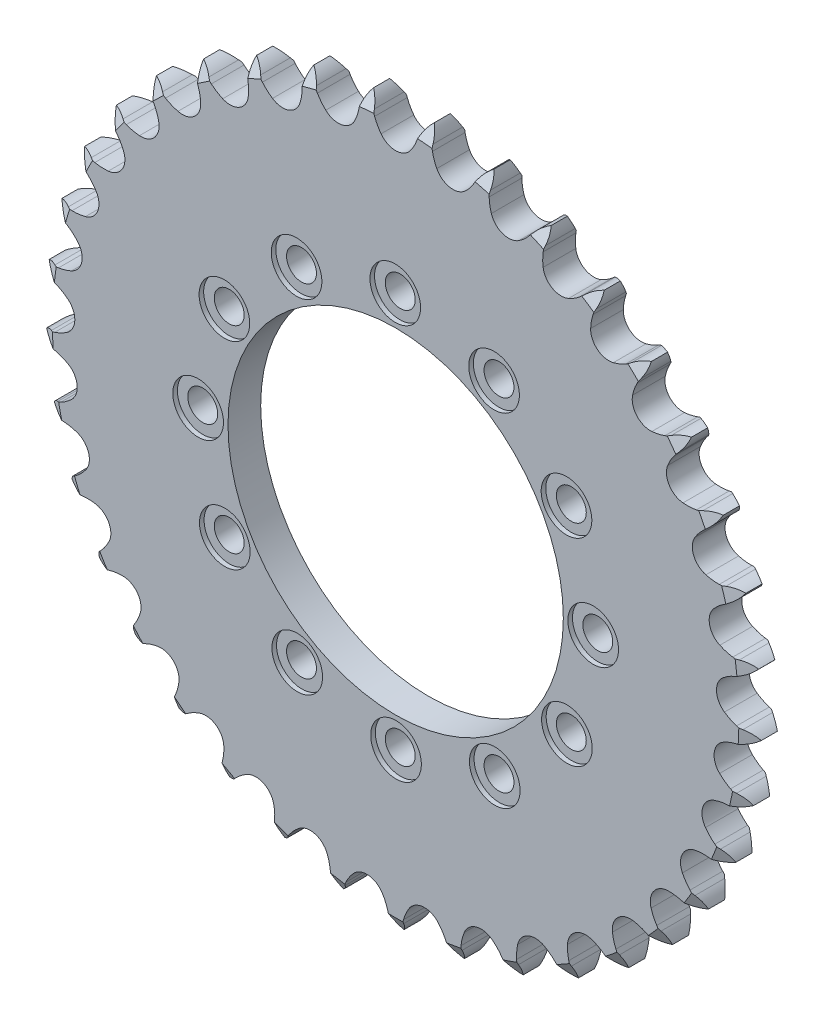
SolidWorks part; units mm, degrees
material "7075-T6 (SN)"
ref_plane "Front Plane" through (0, 0, 0) normal (0, 0, 1) x (1, 0, 0)
ref_plane "Top Plane" through (0, 0, 0) normal (0, 1, 0) x (1, 0, 0)
ref_plane "Right Plane" through (0, 0, 0) normal (1, 0, 0) x (0, 0, -1)
sketch "Work Sketch" plane through (0, 0, 0) normal (0, 0, 1) x (1, 0, 0)
  line L0 (0, 0) -> (0, 160.4542) construction
  line L1 (-112.0919, 74.8768) -> (87.2579, 74.8768) construction
  line L2 (5.0965, 120.8822) -> (5.0965, 112.9699) construction
  line L3 (-12.8497, 78.6648) -> (16.7256, 78.6648) construction
  line L4 (5.0965, 78.6648) -> (-6.0814, 70.3569) construction
  line L5 (5.0965, 78.6648) -> (-4.646, 75.0928) construction
  line L6 (-4.646, 75.0928) -> (-6.919, 81.2921)
  line L7 (-11.5114, 73.9344) -> (-7.1525, 73.9344) construction
  line L8 (-11.0725, 124.7602) -> (-11.0725, 110.2345) construction
  line L9 (0, 0) -> (-3.6257, 42.5992) construction
  circle A0 centre (0, 0) radius 74.8768
  circle A1 centre (0, 74.8768) radius 4.0088
  arc A2 (-4.646, 75.0928) -> (-3.2175, 72.4855) centre (5.0746, 78.7238) ccw
  circle A3 centre (-11.0725, 73.9344) radius 6.4324
  point P23 (-3.2175, 72.4855)
  dimension "D1" = 149.7537
  dimension "D8" = 10.3767
  dimension "D2" = 8.0177
  dimension "D3" = 5.0965
  dimension "D4" = 3.788
  dimension "D5" = 36.622
  dimension "D6" = 16.486
  dimension "D7" = 10.3767
  dimension "D9" = 0.9424
  dimension "D10" = 11.0725
  dimension "D11" = 4.865
sketch "Teeth Sketch" plane through (0, 0, 0) normal (0, 0, 1) x (1, 0, 0)
  line L0 (5.0332, 76.1487) -> (4.646, 75.0928)
  line L1 (-7.8902, 92.7037) -> (-5.0419, 59.2379) construction
  line L2 (0, 0) -> (-11.4893, 132.2573) construction
  line L3 (7.9084, 75.904) -> (8.1115, 74.7978)
  line L4 (16961.1849, -199279.4977) -> (-16964.8106, 199322.0969) construction
  line L5 (0, 146.3285) -> (0, 56.9858) construction
  line L6 (17.83, 74.2028) -> (17.27, 73.2274)
  line L7 (0, -200000) -> (0, 200160.4542) construction
  line L8 (20.6225, 73.4756) -> (20.6357, 72.3511)
  line L9 (-4.646, 75.0928) -> (-6.919, 81.2921) construction
  line L10 (43.9221, 62.4084) -> (43.56, 61.3436)
  line L11 (-5.0332, 76.1487) -> (-4.646, 75.0928)
  line L12 (30.1138, 70.1221) -> (29.397, 69.2555)
  line L13 (32.7433, 68.9336) -> (32.5663, 67.8229)
  line L14 (41.5314, 64.0242) -> (40.6784, 63.2912)
  line L15 (51.7541, 56.0845) -> (50.7896, 55.5061)
  line L16 (53.8374, 54.0878) -> (53.3005, 53.0996)
  line L17 (60.488, 46.5312) -> (59.4396, 46.1242)
  line L18 (62.2039, 44.2112) -> (61.5077, 43.3279)
  line L19 (67.4818, 35.6394) -> (66.3796, 35.4154)
  line L20 (68.7809, 33.0628) -> (67.9454, 32.3098)
  line L21 (72.5342, 23.7223) -> (71.4101, 23.6878)
  line L22 (73.3792, 20.9632) -> (72.4285, 20.3623)
  line L23 (75.4999, 11.1227) -> (74.3862, 11.2787)
  line L24 (75.8665, 8.2605) -> (74.8279, 7.8289)
  line L25 (76.2937, -1.7968) -> (75.2223, -1.4548)
  line L26 (76.1712, -4.6798) -> (75.0747, -4.9297)
  line L27 (74.8926, -14.6647) -> (73.8944, -14.1465)
  line L28 (74.2847, -17.4855) -> (73.1617, -17.5465)
  line L29 (71.337, -27.1106) -> (70.4407, -26.4313)
  line L30 (70.2611, -29.7882) -> (69.1439, -29.6585)
  line L31 (65.7292, -38.7767) -> (64.9606, -37.9556)
  line L32 (64.2162, -41.2339) -> (63.1371, -40.9172)
  line L33 (58.2304, -49.3272) -> (57.6117, -48.3881)
  line L34 (56.324, -51.4934) -> (55.3138, -50.9989)
  line L35 (49.0565, -58.4587) -> (48.6054, -57.4285)
  line L36 (46.8114, -60.2715) -> (45.8993, -59.6134)
  line L37 (38.4713, -65.9084) -> (38.2008, -64.8168)
  line L38 (35.9521, -67.3157) -> (35.1644, -66.513)
  line L39 (26.7794, -71.462) -> (26.6972, -70.3404)
  line L40 (24.0586, -72.4234) -> (23.4179, -71.499)
  line L41 (14.317, -74.9599) -> (14.4256, -73.8404)
  line L42 (11.4729, -75.4475) -> (10.9976, -74.4282)
  line L43 (1.4428, -76.3012) -> (1.739, -75.2163)
  line L44 (-1.4428, -76.3012) -> (-1.739, -75.2163)
  line L45 (-11.4729, -75.4475) -> (-10.9976, -74.4282)
  line L46 (-14.317, -74.9599) -> (-14.4256, -73.8404)
  line L47 (-24.0586, -72.4234) -> (-23.4179, -71.499)
  line L48 (-26.7794, -71.462) -> (-26.6972, -70.3404)
  line L49 (-35.9521, -67.3157) -> (-35.1644, -66.513)
  line L50 (-38.4713, -65.9084) -> (-38.2008, -64.8168)
  line L51 (-46.8114, -60.2715) -> (-45.8993, -59.6134)
  line L52 (-49.0565, -58.4587) -> (-48.6054, -57.4285)
  line L53 (-56.324, -51.4934) -> (-55.3138, -50.9989)
  line L54 (-58.2304, -49.3272) -> (-57.6117, -48.3881)
  line L55 (-64.2162, -41.2339) -> (-63.1371, -40.9172)
  line L56 (-65.7292, -38.7767) -> (-64.9606, -37.9556)
  line L57 (-70.2611, -29.7882) -> (-69.1439, -29.6585)
  line L58 (-71.337, -27.1106) -> (-70.4407, -26.4313)
  line L59 (-74.2847, -17.4855) -> (-73.1617, -17.5465)
  line L60 (-74.8926, -14.6647) -> (-73.8944, -14.1465)
  line L61 (-76.1712, -4.6798) -> (-75.0747, -4.9297)
  line L62 (-76.2937, -1.7968) -> (-75.2223, -1.4548)
  line L63 (-75.8665, 8.2605) -> (-74.8279, 7.8289)
  line L64 (-75.4999, 11.1227) -> (-74.3862, 11.2787)
  line L65 (-73.3792, 20.9632) -> (-72.4285, 20.3623)
  line L66 (-72.5342, 23.7223) -> (-71.4101, 23.6878)
  line L67 (-68.7809, 33.0628) -> (-67.9454, 32.3098)
  line L68 (-67.4818, 35.6394) -> (-66.3796, 35.4154)
  line L69 (-62.2039, 44.2112) -> (-61.5077, 43.3279)
  line L70 (-60.488, 46.5312) -> (-59.4396, 46.1242)
  line L71 (-53.8374, 54.0878) -> (-53.3005, 53.0996)
  line L72 (-51.7541, 56.0845) -> (-50.7896, 55.5061)
  line L73 (-43.9221, 62.4084) -> (-43.56, 61.3436)
  line L74 (-41.5314, 64.0242) -> (-40.6784, 63.2912)
  line L75 (-32.7433, 68.9336) -> (-32.5663, 67.8229)
  line L76 (-30.1138, 70.1221) -> (-29.397, 69.2555)
  line L77 (-20.6225, 73.4756) -> (-20.6357, 72.3511)
  line L78 (-17.83, 74.2028) -> (-17.27, 73.2274)
  line L79 (-7.9084, 75.904) -> (-8.1115, 74.7978)
  arc A0 (-6.8438, 78.7815) -> (-5.0332, 76.1487) centre (-11.0725, 73.9344) cw
  circle A1 centre (-11.0725, 73.9344) radius 6.4324 construction
  arc A2 (-3.2175, 72.4855) -> (-4.646, 75.0928) centre (5.0746, 78.7238) cw
  arc A3 (-4.646, 75.0928) -> (-3.2175, 72.4855) centre (5.0746, 78.7238) ccw construction
  circle A4 centre (0, 74.8768) radius 4.0088 construction
  arc A5 (-3.2175, 72.4855) -> (3.2175, 72.4855) centre (0, 74.8768) ccw
  arc A6 (3.2175, 72.4855) -> (4.646, 75.0928) centre (-5.0746, 78.7238) ccw
  arc A7 (6.8438, 78.7815) -> (5.0332, 76.1487) centre (11.0725, 73.9344) ccw
  arc A8 (6.5688, 78.8049) -> (7.9084, 75.904) centre (1.5818, 74.7422) cw
  arc A9 (9.0789, 71.9866) -> (8.1115, 74.7978) centre (18.306, 76.7339) cw
  arc A10 (9.0789, 71.9866) -> (15.4213, 70.8991) centre (12.6542, 73.7998) ccw
  arc A11 (15.4213, 70.8991) -> (17.27, 73.2274) centre (8.3028, 78.4491) ccw
  arc A12 (20.0595, 76.4917) -> (17.83, 74.2028) centre (23.4082, 70.9997) ccw
  arc A13 (19.7924, 76.5613) -> (20.6225, 73.4756) centre (14.1905, 73.3998) cw
  arc A14 (21.1141, 69.4168) -> (20.6357, 72.3511) centre (31.0108, 72.5364) cw
  arc A15 (21.1141, 69.4168) -> (27.1815, 67.273) centre (24.9445, 70.5997) ccw
  arc A16 (27.1815, 67.273) -> (29.397, 69.2555) centre (21.4413, 75.9175) ccw
  arc A17 (32.6981, 72.0014) -> (30.1138, 70.1221) centre (35.0705, 66.0224) ccw
  arc A18 (32.4466, 72.1151) -> (32.7433, 68.9336) centre (26.391, 69.9458) cw
  arc A19 (32.5419, 64.85) -> (32.5663, 67.8229) centre (42.8234, 66.2522) cw
  arc A20 (32.5419, 64.85) -> (38.1597, 61.7117) centre (36.5171, 65.3685) ccw
  arc A21 (38.1597, 61.7117) -> (40.6784, 63.2912) centre (33.963, 71.2019) ccw
  arc A22 (44.3961, 65.4397) -> (41.5314, 64.0242) centre (45.7239, 59.1458) ccw
  arc A23 (44.1674, 65.5943) -> (43.9221, 62.4084) centre (37.8323, 64.4796) cw
  arc A24 (43.0335, 58.4176) -> (43.56, 61.3436) centre (53.4041, 58.062) cw
  arc A25 (43.0335, 58.4176) -> (48.0401, 54.375) centre (47.0391, 58.2569) ccw
  arc A26 (48.0401, 54.375) -> (50.7896, 55.5061) centre (45.5077, 64.4379) ccw
  arc A27 (54.8169, 56.9954) -> (51.7541, 56.0845) centre (55.0619, 50.5677) ccw
  arc A28 (54.6176, 57.1864) -> (53.8374, 54.0878) centre (48.1852, 57.1584) cw
  arc A29 (52.2871, 50.3046) -> (53.3005, 53.0996) centre (62.4485, 48.2015) cw
  arc A30 (52.2871, 50.3046) -> (56.5385, 45.4741) centre (56.208, 49.4692) ccw
  arc A31 (56.5385, 45.4741) -> (59.4396, 46.1242) centre (55.7431, 55.8202) ccw
  arc A32 (63.6606, 46.9115) -> (60.488, 46.5312) centre (62.8158, 40.5348) ccw
  arc A33 (63.4965, 47.1334) -> (62.2039, 44.2112) centre (57.152, 48.1929) cw
  arc A34 (60.0365, 40.7444) -> (61.5077, 43.3279) centre (69.6963, 36.9543) cw
  arc A35 (60.0365, 40.7444) -> (63.4104, 35.2649) centre (63.7598, 39.2585) ccw
  arc A36 (63.4104, 35.2649) -> (66.3796, 35.4154) centre (64.375, 45.5967) ccw
  arc A37 (70.673, 35.478) -> (67.4818, 35.6394) centre (68.7627, 29.3358) ccw
  arc A38 (70.5488, 35.7245) -> (68.7809, 33.0628) centre (64.4745, 37.841) cw
  arc A39 (66.0588, 30.0121) -> (67.9454, 32.3098) centre (74.9391, 24.644) cw
  arc A40 (66.0588, 30.0121) -> (68.4581, 24.0412) centre (69.4774, 27.9183) ccw
  arc A41 (68.4581, 24.0412) -> (71.4101, 23.6878) centre (71.1549, 34.0614) ccw
  arc A42 (75.6523, 23.0239) -> (72.5342, 23.7223) centre (72.7314, 17.2929) ccw
  arc A43 (75.5714, 23.2878) -> (73.3792, 20.9632) centre (69.9423, 26.4004) cw
  arc A44 (70.1807, 18.4164) -> (72.4285, 20.3623) centre (78.026, 11.6248) cw
  arc A45 (70.1807, 18.4164) -> (71.5364, 12.1259) centre (73.1963, 15.775) ccw
  arc A46 (71.5364, 12.1259) -> (74.3862, 11.2787) centre (75.8878, 21.5462) ccw
  arc A47 (78.4551, 9.9074) -> (75.4999, 11.1227) centre (74.6077, 4.7525) ccw
  arc A48 (78.4201, 10.1812) -> (75.8665, 8.2605) centre (73.3979, 14.2004) cw
  arc A49 (72.2836, 6.2909) -> (74.8279, 7.8289) centre (78.8683, -1.7289) cw
  arc A50 (72.2836, 6.2909) -> (72.5567, -0.1382) centre (74.8094, 3.1779) ccw
  arc A51 (72.5567, -0.1382) -> (75.2223, -1.4548) centre (78.4375, 8.4112) ccw
  arc A52 (79.001, -3.4941) -> (76.2937, -1.7968) centre (74.3377, -7.9246) ccw
  arc A53 (79.0127, -3.2183) -> (76.1712, -4.6798) centre (74.742, 1.5918) cw
  arc A54 (72.307, -6.0155) -> (75.0747, -4.9297) centre (77.4416, -15.0328) cw
  arc A55 (72.307, -6.0155) -> (71.4897, -12.3983) centre (74.2704, -9.5107) ccw
  arc A56 (71.4897, -12.3983) -> (73.8944, -14.1465) centre (78.7308, -4.9658) ccw
  arc A57 (77.2741, -16.795) -> (74.8926, -14.6647) centre (71.9292, -20.3738) ccw
  arc A58 (77.3323, -16.5252) -> (74.2847, -17.4855) centre (73.9359, -11.0626) cw
  arc A59 (70.2503, -18.149) -> (73.1617, -17.5465) centre (73.7872, -27.9043) cw
  arc A60 (70.2503, -18.149) -> (68.366, -24.3018) centre (71.5947, -21.9256) ccw
  arc A61 (68.366, -24.3018) -> (70.4407, -26.4313) centre (76.7591, -18.2) ccw
  arc A62 (73.3243, -29.6129) -> (71.337, -27.1106) centre (67.4514, -32.2368) ccw
  arc A63 (73.4272, -29.3567) -> (70.2611, -29.7882) centre (71.0028, -23.3987) cw
  arc A64 (66.1727, -29.7603) -> (69.1439, -29.6585) centre (68.0099, -39.973) cw
  arc A65 (66.1727, -29.7603) -> (63.2756, -35.5062) centre (66.8595, -33.7098) ccw
  arc A66 (63.2756, -35.5062) -> (64.9606, -37.9556) centre (72.5792, -30.9105) ccw
  arc A67 (67.265, -41.5788) -> (65.7292, -38.7767) centre (61.0331, -43.1725) ccw
  arc A68 (67.4097, -41.3437) -> (64.2162, -41.2339) centre (66.0271, -35.0616) cw
  arc A69 (60.1913, -40.5154) -> (63.1371, -40.9172) centre (60.2762, -50.8918) cw
  arc A70 (60.1913, -40.5154) -> (56.3649, -45.6891) centre (60.2008, -44.5243) ccw
  arc A71 (56.3649, -45.6891) -> (57.6117, -48.3881) centre (66.3113, -42.7318) ccw
  arc A72 (59.2706, -52.3485) -> (58.2304, -49.3272) centre (52.859, -52.8661) ccw
  arc A73 (59.4529, -52.1413) -> (56.324, -51.4934) centre (59.1519, -45.7159) cw
  arc A74 (52.4784, -50.105) -> (55.3138, -50.9989) centre (50.8084, -60.3465) cw
  arc A75 (52.4784, -50.105) -> (47.8326, -54.5576) centre (51.8102, -54.0578) ccw
  arc A76 (47.8326, -54.5576) -> (48.6054, -57.4285) centre (58.1357, -53.3238) ccw
  arc A77 (49.5711, -61.6123) -> (49.0565, -58.4587) centre (43.1643, -61.0389) ccw
  arc A78 (49.7858, -61.4389) -> (46.8114, -60.2715) centre (50.5751, -55.0551) cw
  arc A79 (43.2557, -58.2532) -> (45.8993, -59.6134) centre (39.879, -68.0651) cw
  arc A80 (43.2557, -58.2532) -> (37.9243, -61.8566) centre (41.9291, -62.0362) ccw
  arc A81 (37.9243, -61.8566) -> (38.2008, -64.8168) centre (48.2877, -62.3818) ccw
  arc A82 (38.4455, -69.1036) -> (38.4713, -65.9084) centre (32.2278, -67.4557) ccw
  arc A83 (38.6865, -68.969) -> (35.9521, -67.3157) centre (40.5432, -62.8104) cw
  arc A84 (32.7887, -64.7255) -> (35.1644, -66.513) centre (27.8023, -73.8256) cw
  arc A85 (32.7887, -64.7255) -> (26.925, -67.3761) centre (30.8419, -68.2299) ccw
  arc A86 (26.925, -67.3761) -> (26.6972, -70.3404) centre (37.0506, -69.6452) ccw
  arc A87 (26.2139, -74.6069) -> (26.7794, -71.462) centre (20.3641, -71.9319) ccw
  arc A88 (26.4742, -74.515) -> (24.0586, -72.4234) centre (29.345, -68.7588) cw
  arc A89 (21.3784, -69.3358) -> (23.4179, -71.499) centre (14.9258, -77.4623) cw
  arc A90 (21.3784, -69.3358) -> (15.1511, -70.9573) centre (18.8673, -72.4608) ccw
  arc A91 (15.1511, -70.9573) -> (14.4256, -73.8404) centre (24.7475, -74.905) ccw
  arc A92 (13.2282, -77.964) -> (14.317, -74.9599) centre (7.9147, -74.3388) ccw
  arc A93 (13.5003, -77.9173) -> (11.4729, -75.4475) centre (17.3027, -72.7291) cw
  arc A94 (9.3531, -71.9515) -> (10.9976, -74.4282) centre (1.6199, -78.8706) cw
  arc A95 (9.3531, -71.9515) -> (2.9413, -72.4972) centre (6.35, -74.6071) ccw
  arc A96 (2.9413, -72.4972) -> (1.739, -75.2163) centre (11.7326, -78.0099) ccw
  arc A97 (-0.138, -79.0781) -> (1.4428, -76.3012) centre (-4.7625, -74.6071) ccw
  arc A98 (0.138, -79.0781) -> (-1.4428, -76.3012) centre (4.7625, -74.6071) cw
  arc A99 (-2.9413, -72.4972) -> (-1.739, -75.2163) centre (-11.7326, -78.0099) cw
  arc A100 (-2.9413, -72.4972) -> (-9.3531, -71.9515) centre (-6.35, -74.6071) ccw
  arc A101 (-9.3531, -71.9515) -> (-10.9976, -74.4282) centre (-1.6199, -78.8706) ccw
  arc A102 (-13.5003, -77.9173) -> (-11.4729, -75.4475) centre (-17.3027, -72.7291) ccw
  arc A103 (-13.2282, -77.964) -> (-14.317, -74.9599) centre (-7.9147, -74.3388) cw
  arc A104 (-15.1511, -70.9573) -> (-14.4256, -73.8404) centre (-24.7475, -74.905) cw
  arc A105 (-15.1511, -70.9573) -> (-21.3784, -69.3358) centre (-18.8673, -72.4608) ccw
  arc A106 (-21.3784, -69.3358) -> (-23.4179, -71.499) centre (-14.9258, -77.4623) ccw
  arc A107 (-26.4742, -74.515) -> (-24.0586, -72.4234) centre (-29.345, -68.7588) ccw
  arc A108 (-26.2139, -74.6069) -> (-26.7794, -71.462) centre (-20.3641, -71.9319) cw
  arc A109 (-26.925, -67.3761) -> (-26.6972, -70.3404) centre (-37.0506, -69.6452) cw
  arc A110 (-26.925, -67.3761) -> (-32.7887, -64.7255) centre (-30.8419, -68.2299) ccw
  arc A111 (-32.7887, -64.7255) -> (-35.1644, -66.513) centre (-27.8023, -73.8256) ccw
  arc A112 (-38.6865, -68.969) -> (-35.9521, -67.3157) centre (-40.5432, -62.8104) ccw
  arc A113 (-38.4455, -69.1036) -> (-38.4713, -65.9084) centre (-32.2278, -67.4557) cw
  arc A114 (-37.9243, -61.8566) -> (-38.2008, -64.8168) centre (-48.2877, -62.3818) cw
  arc A115 (-37.9243, -61.8566) -> (-43.2557, -58.2532) centre (-41.9291, -62.0362) ccw
  arc A116 (-43.2557, -58.2532) -> (-45.8993, -59.6134) centre (-39.879, -68.0651) ccw
  arc A117 (-49.7858, -61.4389) -> (-46.8114, -60.2715) centre (-50.5751, -55.0551) ccw
  arc A118 (-49.5711, -61.6123) -> (-49.0565, -58.4587) centre (-43.1643, -61.0389) cw
  arc A119 (-47.8326, -54.5576) -> (-48.6054, -57.4285) centre (-58.1357, -53.3238) cw
  arc A120 (-47.8326, -54.5576) -> (-52.4784, -50.105) centre (-51.8102, -54.0578) ccw
  arc A121 (-52.4784, -50.105) -> (-55.3138, -50.9989) centre (-50.8084, -60.3465) ccw
  arc A122 (-59.4529, -52.1413) -> (-56.324, -51.4934) centre (-59.1519, -45.7159) ccw
  arc A123 (-59.2706, -52.3485) -> (-58.2304, -49.3272) centre (-52.859, -52.8661) cw
  arc A124 (-56.3649, -45.6891) -> (-57.6117, -48.3881) centre (-66.3113, -42.7318) cw
  arc A125 (-56.3649, -45.6891) -> (-60.1913, -40.5154) centre (-60.2008, -44.5243) ccw
  arc A126 (-60.1913, -40.5154) -> (-63.1371, -40.9172) centre (-60.2762, -50.8918) ccw
  arc A127 (-67.4097, -41.3437) -> (-64.2162, -41.2339) centre (-66.0271, -35.0616) ccw
  arc A128 (-67.265, -41.5788) -> (-65.7292, -38.7767) centre (-61.0331, -43.1725) cw
  arc A129 (-63.2756, -35.5062) -> (-64.9606, -37.9556) centre (-72.5792, -30.9105) cw
  arc A130 (-63.2756, -35.5062) -> (-66.1727, -29.7603) centre (-66.8595, -33.7098) ccw
  arc A131 (-66.1727, -29.7603) -> (-69.1439, -29.6585) centre (-68.0099, -39.973) ccw
  arc A132 (-73.4272, -29.3567) -> (-70.2611, -29.7882) centre (-71.0028, -23.3987) ccw
  arc A133 (-73.3243, -29.6129) -> (-71.337, -27.1106) centre (-67.4514, -32.2368) cw
  arc A134 (-68.366, -24.3018) -> (-70.4407, -26.4313) centre (-76.7591, -18.2) cw
  arc A135 (-68.366, -24.3018) -> (-70.2503, -18.149) centre (-71.5947, -21.9256) ccw
  arc A136 (-70.2503, -18.149) -> (-73.1617, -17.5465) centre (-73.7872, -27.9043) ccw
  arc A137 (-77.3323, -16.5252) -> (-74.2847, -17.4855) centre (-73.9359, -11.0626) ccw
  arc A138 (-77.2741, -16.795) -> (-74.8926, -14.6647) centre (-71.9292, -20.3738) cw
  arc A139 (-71.4897, -12.3983) -> (-73.8944, -14.1465) centre (-78.7308, -4.9658) cw
  arc A140 (-71.4897, -12.3983) -> (-72.307, -6.0155) centre (-74.2704, -9.5107) ccw
  arc A141 (-72.307, -6.0155) -> (-75.0747, -4.9297) centre (-77.4416, -15.0328) ccw
  arc A142 (-79.0127, -3.2183) -> (-76.1712, -4.6798) centre (-74.742, 1.5918) ccw
  arc A143 (-79.001, -3.4941) -> (-76.2937, -1.7968) centre (-74.3377, -7.9246) cw
  arc A144 (-72.5567, -0.1382) -> (-75.2223, -1.4548) centre (-78.4375, 8.4112) cw
  arc A145 (-72.5567, -0.1382) -> (-72.2836, 6.2909) centre (-74.8094, 3.1779) ccw
  arc A146 (-72.2836, 6.2909) -> (-74.8279, 7.8289) centre (-78.8683, -1.7289) ccw
  arc A147 (-78.4201, 10.1812) -> (-75.8665, 8.2605) centre (-73.3979, 14.2004) ccw
  arc A148 (-78.4551, 9.9074) -> (-75.4999, 11.1227) centre (-74.6077, 4.7525) cw
  arc A149 (-71.5364, 12.1259) -> (-74.3862, 11.2787) centre (-75.8878, 21.5462) cw
  arc A150 (-71.5364, 12.1259) -> (-70.1807, 18.4164) centre (-73.1963, 15.775) ccw
  arc A151 (-70.1807, 18.4164) -> (-72.4285, 20.3623) centre (-78.026, 11.6248) ccw
  arc A152 (-75.5714, 23.2878) -> (-73.3792, 20.9632) centre (-69.9423, 26.4004) ccw
  arc A153 (-75.6523, 23.0239) -> (-72.5342, 23.7223) centre (-72.7314, 17.2929) cw
  arc A154 (-68.4581, 24.0412) -> (-71.4101, 23.6878) centre (-71.1549, 34.0614) cw
  arc A155 (-68.4581, 24.0412) -> (-66.0588, 30.0121) centre (-69.4774, 27.9183) ccw
  arc A156 (-66.0588, 30.0121) -> (-67.9454, 32.3098) centre (-74.9391, 24.644) ccw
  arc A157 (-70.5488, 35.7245) -> (-68.7809, 33.0628) centre (-64.4745, 37.841) ccw
  arc A158 (-70.673, 35.478) -> (-67.4818, 35.6394) centre (-68.7627, 29.3358) cw
  arc A159 (-63.4104, 35.2649) -> (-66.3796, 35.4154) centre (-64.375, 45.5967) cw
  arc A160 (-63.4104, 35.2649) -> (-60.0365, 40.7444) centre (-63.7598, 39.2585) ccw
  arc A161 (-60.0365, 40.7444) -> (-61.5077, 43.3279) centre (-69.6963, 36.9543) ccw
  arc A162 (-63.4965, 47.1334) -> (-62.2039, 44.2112) centre (-57.152, 48.1929) ccw
  arc A163 (-63.6606, 46.9115) -> (-60.488, 46.5312) centre (-62.8158, 40.5348) cw
  arc A164 (-56.5385, 45.4741) -> (-59.4396, 46.1242) centre (-55.7431, 55.8202) cw
  arc A165 (-56.5385, 45.4741) -> (-52.2871, 50.3046) centre (-56.208, 49.4692) ccw
  arc A166 (-52.2871, 50.3046) -> (-53.3005, 53.0996) centre (-62.4485, 48.2015) ccw
  arc A167 (-54.6176, 57.1864) -> (-53.8374, 54.0878) centre (-48.1852, 57.1584) ccw
  arc A168 (-54.8169, 56.9954) -> (-51.7541, 56.0845) centre (-55.0619, 50.5677) cw
  arc A169 (-48.0401, 54.375) -> (-50.7896, 55.5061) centre (-45.5077, 64.4379) cw
  arc A170 (-48.0401, 54.375) -> (-43.0335, 58.4176) centre (-47.0391, 58.2569) ccw
  arc A171 (-43.0335, 58.4176) -> (-43.56, 61.3436) centre (-53.4041, 58.062) ccw
  arc A172 (-44.1674, 65.5943) -> (-43.9221, 62.4084) centre (-37.8323, 64.4796) ccw
  arc A173 (-44.3961, 65.4397) -> (-41.5314, 64.0242) centre (-45.7239, 59.1458) cw
  arc A174 (-38.1597, 61.7117) -> (-40.6784, 63.2912) centre (-33.963, 71.2019) cw
  arc A175 (-38.1597, 61.7117) -> (-32.5419, 64.85) centre (-36.5171, 65.3685) ccw
  arc A176 (-32.5419, 64.85) -> (-32.5663, 67.8229) centre (-42.8234, 66.2522) ccw
  arc A177 (-32.4466, 72.1151) -> (-32.7433, 68.9336) centre (-26.391, 69.9458) ccw
  arc A178 (-32.6981, 72.0014) -> (-30.1138, 70.1221) centre (-35.0705, 66.0224) cw
  arc A179 (-27.1815, 67.273) -> (-29.397, 69.2555) centre (-21.4413, 75.9175) cw
  arc A180 (-27.1815, 67.273) -> (-21.1141, 69.4168) centre (-24.9445, 70.5997) ccw
  arc A181 (-21.1141, 69.4168) -> (-20.6357, 72.3511) centre (-31.0108, 72.5364) ccw
  arc A182 (-19.7924, 76.5613) -> (-20.6225, 73.4756) centre (-14.1905, 73.3998) ccw
  arc A183 (-20.0595, 76.4917) -> (-17.83, 74.2028) centre (-23.4082, 70.9997) cw
  arc A184 (-15.4213, 70.8991) -> (-17.27, 73.2274) centre (-8.3028, 78.4491) cw
  arc A185 (-15.4213, 70.8991) -> (-9.0789, 71.9866) centre (-12.6542, 73.7998) ccw
  arc A186 (-9.0789, 71.9866) -> (-8.1115, 74.7978) centre (-18.306, 76.7339) ccw
  arc A187 (-6.5688, 78.8049) -> (-7.9084, 75.904) centre (-1.5818, 74.7422) ccw
  point P77 (0, 0)
  dimension "D1" = 4.865
  dimension "D2" = 4.965
  dimension "D3" = 37
extrude "Extrusion" add sketch "Teeth Sketch" along normal blind 7.2136
hole_wizard "M6 Clearance Hole1" positions "Sketch6" profile "Sketch7" hole size "M6" standard "ANSI Metric"
sketch "Sketch6" plane through (0, 0, 0) normal (0, 0, -1) x (-1, 0, 0)
  circle A0 centre (0, 0) radius 43.5
  point P0 (0, 43.5)
  dimension "D1" = 87
sketch "Sketch7" plane through (0, 43.5, 0) normal (1, 0, 0) x (0, 1, 0)
  line L0 (0, 0) -> (0, 19.2548)
  line L1 (0, 19.2548) -> (3.3, 17.272)
  line L2 (3.3, 17.272) -> (3.3, 0)
  line L5 (3.3, 0) -> (0, 0)
  line L10 (0, 19.2548) -> (-3.3, 17.272) construction
  line L11 (0, -6.35) -> (0, 107.95) construction
  dimension "Hole Dia." = 6.6
  dimension "Hole Depth" = 17.272
  dimension "Drill Angle" = 118
pattern_circular "CirPattern1" count 12 over 360 about axis through (0, -0.0877, 0) along (0, 0, 1) of "M6 Clearance Hole1"
sketch "Sketch8" plane through (0, 0, 0) normal (0, 0, -1) x (-1, 0, 0)
  circle A0 centre (0, 0) radius 37
  dimension "D1" = 74
extrude "Cut-Extrude1" cut sketch "Sketch8" against normal through all both and the other way through all
ref_plane "Sprocket Center Plane" through (0, 0, 3.6068) normal (0, 0, 1) x (1, 0, 0)
sketch "Pitch Circle" plane through (0, 0, 3.6068) normal (0, 0, -1) x (-1, 0, 0)
  circle A0 centre (0, 0) radius 74.8768 construction
  dimension "D1" = 149.7537
ref_plane "Center Plane" through (0, 0, 3.6068) normal (0, 0, 1) x (1, 0, 0)
ref_axis "Axis1" through (0, 0, 7.2136) along (0, 0, -1)
sketch "Sketch5" plane through (0, 0, 0) normal (1, 0, 0) x (0, 0, -1)
  line L0 (-1.8288, -78.9308) -> (-5.3848, -78.9308)
  line L1 (-7.2136, -74.4221) -> (0, -74.4221) construction
  line L2 (-5.3848, -78.9308) -> (-5.3848, -75.7372)
  line L3 (-5.3848, -75.7372) -> (-7.2136, -75.7372)
  line L4 (-7.2136, -75.7372) -> (-5.3848, -78.9308)
  line L5 (-7.2136, -75.7372) -> (-7.2136, -78.9308)
  line L6 (-7.2136, -78.9308) -> (-5.3848, -78.9308)
  line L9 (-7.2136, -78.9308) -> (0, -78.9308) construction
  dimension "D1" = 3.556
  dimension "D2" = 3.1936
  dimension "D3" = 1.8288
revolve "Cut-Revolve1" cut sketch "Sketch5" angle 360 about axis through (0, 0, 7.2136) along (0, 0, -1)
mirror "Mirror1" about plane through (0, 0, 3.6068) normal (0, 0, 1) of "Cut-Revolve1"
sketch "Sketch10" plane through (0, 0, 0) normal (0, 0, 1) x (1, 0, 0)
  circle A0 centre (-43.5877, -0.0877) radius 5.588
  dimension "D1" = 11.176
extrude "Cut-Extrude2" cut sketch "Sketch10" against normal blind 1.016 from surface at 7.2136 starting at face at (-37, 0, 7.2136)
pattern_circular "CirPattern2" count 12 over 360 about axis through (0, 0, 0) along (0, 0, 1) of "Cut-Extrude2"
ref_plane "Half Plane" through (0, 0, 3.6068) normal (0, 0, 1) x (1, 0, 0)
sketch "Motor Shaft Sprocket Dimensions" plane through (0, 0, 3.6068) normal (0, 0, 1) x (1, 0, 0)
  line L0 (0, 0) -> (-177.8, 0)
  line L1 (-177.8, 0) -> (-177.8, 23.6982)
  line L2 (-181.4954, 50.9571) -> (-10.0588, 74.1981)
  line L3 (-188.506, -1.6412) -> (-29.1415, -68.9733)
  line L4 (-10.0588, 74.1981) -> (0, 0)
  line L5 (0, 0) -> (-29.1415, -68.9733)
  circle A0 centre (-177.8, 23.6982) radius 27.5082
  circle A1 centre (0, 0) radius 74.8768 construction
  dimension "D3" = 55.0164
  dimension "D1" = 177.8
  dimension "D2" = 23.6982
  dimension "D4" = 210.625
equation "\"P\"= 0.500'//Chain Pitch"
equation "\"N\"= 37'//Number of Teeth"
equation "\"Dr\"= 5 / 16'//Roller Diameter"
equation "\"Ds\"= 1.0005 * \"Dr\" + 0.003'Seating Curve DIameter"
equation "\"R\"= \"Ds\" / 2"
equation "\"A\"= 35 + 60 / \"N\""
equation "\"B\"= 18 - 56 / \"N\""
equation "\"ac\"= 0.8 * \"Dr\""
equation "\"M\"= 0.8 * \"Dr\" * cos ( 35 + 60 / \"N\" )"
equation "\"T\"= 0.8 * \"Dr\" * sin ( 35 + 60 / \"N\" )"
equation "\"E\"= 1.3025 * \"Dr\" + 0.0015"
equation "\"Chordal Length of Arc xy\"= ( 2.605 * \"Dr\" + 0.003 ) * sin ( 9 - 28 / \"N\" )"
equation "\"yz\"= \"Dr\" * ( 1.4 * sin ( 17 - 64 / \"N\" ) - 0.8 * sin ( 18 - 56 / \"N\" ) )"
equation "\"ab\"= 1.4 * \"Dr\""
equation "\"W\"= 1.4 * \"Dr\" * cos ( 180 / \"N\" )"
equation "\"V\"= 1.4 * \"Dr\" * sin ( 180 / \"N\" )"
equation "\"F\"= \"Dr\" * ( 0.8 * cos ( 18 - 56 / \"N\" ) + 1.4 * cos ( 17 - 64 / \"N\" ) - 1.3025 )"
equation "\"H\"= sqr ( \"F\" ^ 2 - ( 1.4 * \"Dr\" - \"P\" / 2 ) ^ 2 )"
equation "\"S\"= \"P\" / 2 * cos ( 180 / \"N\" ) + \"H\" * sin ( 180 / \"N\" )"
equation "\"PD\"= \"P\" / ( sin ( 180 / \"N\" ) )"
equation "\"D1@Work Sketch\" = \"PD\""
equation "\"D3@Work Sketch\" = \"M\""
equation "\"D4@Work Sketch\" = \"T\""
equation "\"D5@Work Sketch\" = \"A\""
equation "\"D6@Work Sketch\" = \"B\""
equation "\"D7@Work Sketch\" = \"E\""
equation "\"D8@Work Sketch\" = \"E\""
equation "\"D9@Work Sketch\" = \"V\""
equation "\"D10@Work Sketch\" = \"W\""
equation "\"D2@Work Sketch\" = \"R\" * 2"
equation "\"D11@Work Sketch\" = 180 / \"N\""
equation "\"D2@Teeth Sketch\" = 180 / \"N\" + 0.1"
equation "\"D3@Teeth Sketch\" = \"N\""
equation "\"Edge Thickness\"=0.5"
equation "\"D1@Pitch Circle\"=\"PD\""
equation "\"ST\"= 0.284'//Sprocket Thickness"
